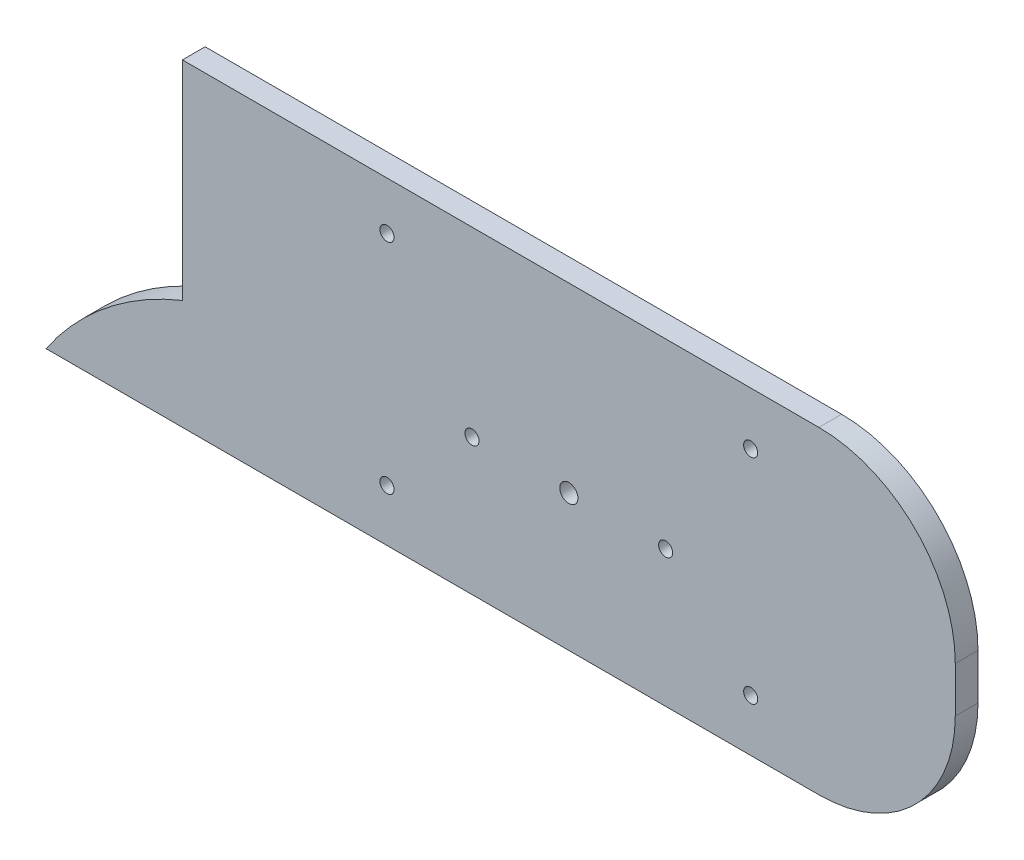
SolidWorks part; units mm, degrees
material "1060 Alloy"
ref_plane "Front Plane" through (0, 0, 0) normal (0, 0, 1) x (1, 0, 0)
ref_plane "Top Plane" through (0, 0, 0) normal (0, 1, 0) x (1, 0, 0)
ref_plane "Right Plane" through (0, 0, 0) normal (1, 0, 0) x (0, 0, -1)
sketch "Sketch2" plane through (0, 0, 0) normal (0, 0, 1) x (1, 0, 0)
  line L0 (0, 0) -> (431.8, 0)
  line L1 (76.2, 0) -> (76.2, 142.4009) construction
  line L2 (152.4, 0) -> (152.4, 186.487) construction
  line L9 (431.8, 177.8) -> (152.4, 177.8)
  line L14 (508, 76.2) -> (508, 101.6)
  line L15 (152.4, 177.8) -> (76.2, 177.8)
  line L16 (76.2, 177.8) -> (76.2, 61.4013)
  arc A5 (0, 0) -> (76.2, 61.4013) centre (138.3869, -93.7571) cw
  arc A6 (431.8, 0) -> (508, 76.2) centre (431.8, 76.2) ccw
  arc A7 (508, 101.6) -> (431.8, 177.8) centre (431.8, 101.6) ccw
  dimension "D6" = 167.1566
  dimension "D7" = 142.4009
  dimension "D5" = 177.8
  dimension "D1" = 76.2
  dimension "D4" = 431.8
  dimension "D9" = 138.3869
  dimension "D2" = 76.2
  dimension "D3" = 152.4
  dimension "D8" = 186.487
extrude "Boss-Extrude1" add sketch "Sketch2" along normal blind 12.7
sketch "Sketch3" plane through (0, 0, 0) normal (0, 0, -1) x (-1, 0, 0)
  line L0 (-76.2, 189.7623) -> (-76.2, -31.0498) construction
  line L1 (-76.2, 29.0821) -> (-494.3071, 29.0821) construction
  line L2 (-431.8, 0) -> (-433.2183, 177.7868) construction
  line L3 (0, 0) -> (-431.8, 0) construction
  arc A0 (-431.8, 177.8) -> (-508, 101.6) centre (-431.8, 101.6) ccw construction
  circle A1 centre (-190.5, 29.0821) radius 3.937
  circle A4 centre (-393.7, 29.0821) radius 3.937
  circle A7 centre (-393.7, 148.336) radius 3.937
  circle A8 centre (-190.5, 151.0021) radius 3.937
  point P15 (0, 0)
  point P17 (-102.0433, -12.1128)
  dimension "D5" = 7.874
  dimension "D10" = 114.3
  dimension "D1" = 76.2
  dimension "D2" = 177.7868
  dimension "D3" = 29.0821
  dimension "D4" = 114.3
  dimension "D8" = 317.5
  dimension "D9" = 121.92
  dimension "D11" = 29.0821
  dimension "D6" = 393.7
  dimension "D7" = 148.336
extrude "Cut-Extrude1" cut sketch "Sketch3" against normal through all
sketch "Sketch4" plane through (0, 0, 12.7) normal (0, 0, 1) x (1, 0, 0)
  line L0 (292.1, 0) -> (292.1, 177.8) construction
  line L1 (0, 0) -> (431.8, 0) construction
  line L2 (431.8, 177.8) -> (76.2, 177.8) construction
  line L3 (76.2, 76.2) -> (508, 76.2) construction
  line L5 (76.2, 177.8) -> (76.2, 61.4013) construction
  circle A0 centre (292.1, 76.2) radius 5.08
  circle A1 centre (237.998, 76.2) radius 3.937
  circle A2 centre (346.202, 76.2) radius 3.937
  dimension "D1" = 10.16
  dimension "D4" = 7.874
  dimension "D5" = 7.874
  dimension "D6" = 54.102
  dimension "D7" = 54.102
  dimension "D2" = 292.1
  dimension "D3" = 76.2
extrude "Cut-Extrude2" cut sketch "Sketch4" against normal through all
equation "\"0.5n\"=0.25"
equation "\".5n\"=0.25"
